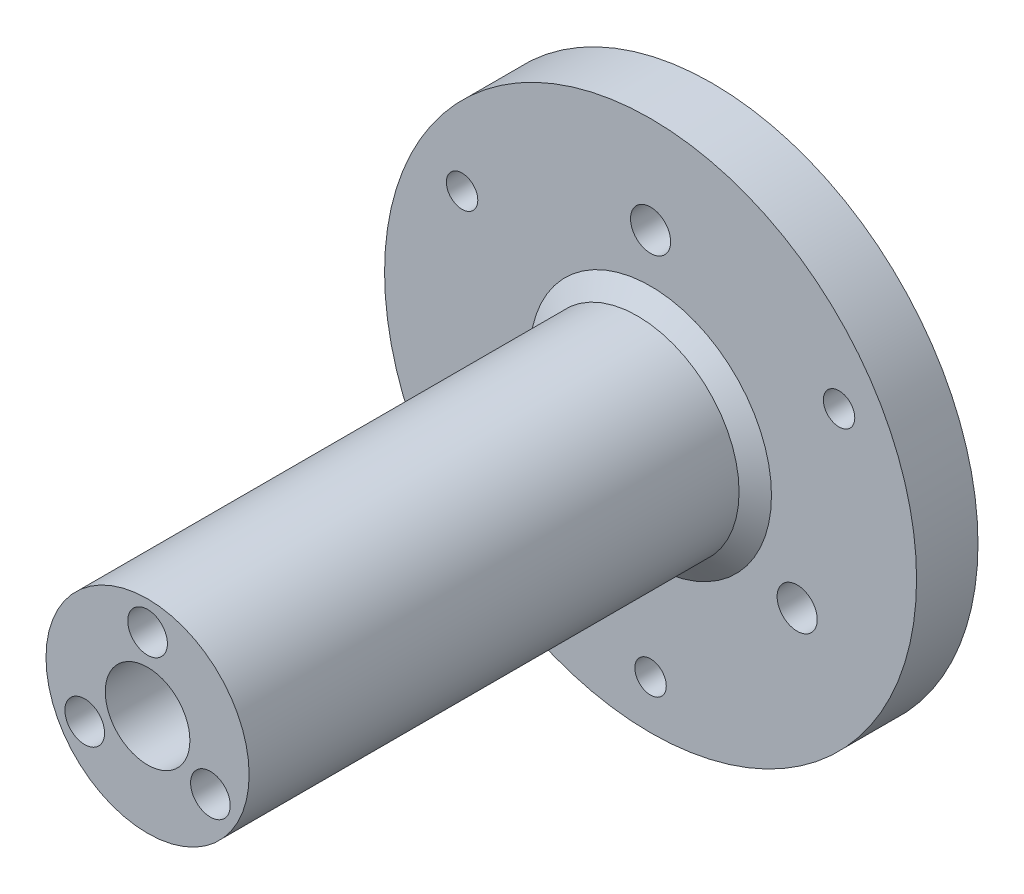
SolidWorks part; units mm, degrees
ref_plane "Plan de face" through (0, 0, 0) normal (0, 0, 1) x (1, 0, 0)
ref_plane "Plan de dessus" through (0, 0, 0) normal (0, 1, 0) x (1, 0, 0)
ref_plane "Plan de droite" through (0, 0, 0) normal (1, 0, 0) x (0, 0, -1)
sketch "Esquisse2" plane through (0, 0, 0) normal (0, 0, 1) x (1, 0, 0)
  circle A0 centre (0, 0) radius 7.5
  circle A1 centre (0, 0) radius 4
  dimension "D1" = 15
  dimension "D2" = 8
sketch "Esquisse1" plane through (0, 0, 0) normal (0, 0, 1) x (1, 0, 0)
  line L0 (-17.5, 10.1036) -> (0, -20.2073) construction
  line L1 (0, -20.2073) -> (17.5, 10.1036) construction
  line L2 (17.5, 10.1036) -> (-17.5, 10.1036) construction
  line L3 (16.0524, 9.2678) -> (-8.4583, -4.8834) construction
  line L4 (0.0575, -0.0332) -> (-30.6383, 17.689) construction
  circle A0 centre (-17.5, 10.1036) radius 1.625
  circle A1 centre (0, -20.2073) radius 1.625
  circle A2 centre (17.5, 10.1036) radius 1.625
  dimension "D2" = 3.25
  dimension "D1" = 35
sketch "Esquisse3" plane through (0, 0, 0) normal (0, 0, 1) x (1, 0, 0)
  line L5 (-19.4856, 11.25) -> (19.4856, 11.25) construction
  line L6 (19.4856, 11.25) -> (0, -22.5) construction
  line L7 (0, -22.5) -> (-19.4856, 11.25) construction
  circle A0 centre (-19.4856, 11.25) radius 1.625
  circle A1 centre (19.4856, 11.25) radius 1.625
  circle A2 centre (0, -22.5) radius 1.625
  circle A3 centre (0, -20.2073) radius 1.625 construction
  circle A4 centre (17.5, 10.1036) radius 1.625 construction
  circle A5 centre (-17.5, 10.1036) radius 1.625 construction
  circle A7 centre (0, 0) radius 22.5
  circle A8 centre (0, 0) radius 27.5
  circle A10 centre (0, 0) radius 7.6
  dimension "D2" = 15.2
  dimension "D1" = 45
  dimension "D3" = 55
extrude "Boss.-Extru.1" add sketch "Esquisse3" along normal blind 6.35 contours A8 A7 A1 A2 A0 | A1 A7 A0 A2 A10 region at (-17.5074, 12.3449, 0) region at (-26.7222, 0, 0)
sketch "Esquisse4" plane through (0, 0, 6.35) normal (0, 0, 1) x (1, 0, 0)
  circle A2 centre (0, 0) radius 7.6
  circle A3 centre (0, 0) radius 10.5
  circle A4 centre (0, 0) radius 7.6 construction
  dimension "D1" = 21
extrude "Boss.-Extru.2" add sketch "Esquisse4" along normal blind 45
sketch "Sketch1" plane through (0, 0, 51.35) normal (0, 0, 1) x (1, 0, 0)
  circle A0 centre (0, 0) radius 10.5
  circle A1 centre (0, 0) radius 4.375
  circle A2 centre (0, 0) radius 10.5 construction
  dimension "D1" = 8.75
extrude "Boss-Extrude1" add sketch "Sketch1" along normal blind 7
sketch "Sketch2" plane through (0, 0, 58.35) normal (0, 0, 1) x (1, 0, 0)
  line L0 (-6.4952, -3.75) -> (0, 7.5) construction
  line L1 (0, 7.5) -> (6.4952, -3.75) construction
  line L2 (-3.2476, 1.875) -> (6.4952, -3.75) construction
  line L3 (-6.4952, -3.75) -> (3.2476, 1.875) construction
  line L4 (-6.4952, -3.75) -> (6.4952, -3.75) construction
  circle A0 centre (0, 7.5) radius 2.05
  circle A1 centre (-6.4952, -3.75) radius 2.05
  circle A2 centre (6.4952, -3.75) radius 2.05
  circle A3 centre (0, 0) radius 7.5
  point P7 (0, 0)
  dimension "D1" = 4.1
  dimension "D2" = 15
extrude "Cut-Extrude1" cut sketch "Sketch2" against normal blind 6 contours A3 A0 | A0 A3 | A3 A1 | A1 A3 | A3 A2 | A2 A3 region at (0, 8.3176, 58.35) region at (0, 6.5815, 58.35) region at (-7.2033, -4.1588, 58.35) region at (-5.6997, -3.2907, 58.35) region at (5.6997, -3.2907, 58.35) region at (7.2033, -4.1588, 58.35)
chamfer "Chamfer2" distance 4 angle 55 1 edges at (7.6, 0, 51.35) first distance on face at (4.375, 0, 51.35)
chamfer "Chamfer3" distance 2 angle 34 1 edges at (10.5, 0, 6.35) first distance on face at (27.5, 0, 6.35)
sketch "Sketch3" plane through (0, 0, 6.35) normal (0, 0, 1) x (1, 0, 0)
  line L0 (-15.1554, -8.75) -> (0, 17.5) construction
  line L1 (0, 17.5) -> (15.1554, -8.75) construction
  line L2 (15.1554, -8.75) -> (-15.1554, -8.75) construction
  circle A0 centre (0, 17.5) radius 2.075
  circle A1 centre (-15.1554, -8.75) radius 2.075
  circle A2 centre (15.1554, -8.75) radius 2.075
  circle A3 centre (0, 0) radius 17.5
  dimension "D1" = 4.15
  dimension "D2" = 35
extrude "Cut-Extrude2" cut sketch "Sketch3" against normal blind 8 contours A0 A3 | A3 A1 | A3 A2 | A2 A3 | A0 | A1 region at (0, 16.5976, 6.35) region at (-15.8986, -9.1791, 6.35) region at (14.3739, -8.2988, 6.35) region at (15.8986, -9.1791, 6.35)
